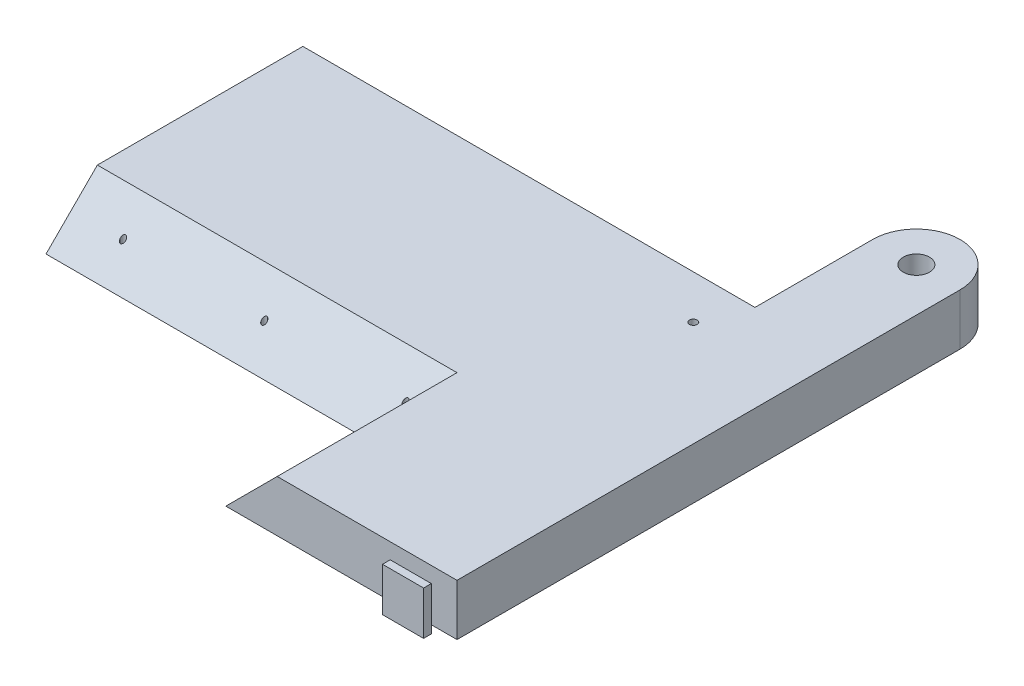
SolidWorks part; units mm, degrees
ref_plane "Front Plane" through (0, 0, 0) normal (0, 0, 1) x (1, 0, 0)
ref_plane "Top Plane" through (0, 0, 0) normal (0, 1, 0) x (1, 0, 0)
ref_plane "Right Plane" through (0, 0, 0) normal (1, 0, 0) x (0, 0, -1)
sketch "CornerSketch1" plane through (0, 0, 0) normal (0, 1, 0) x (1, 0, 0)
  line L0 (210, -50) -> (120, -50)
  line L2 (0, 100) -> (176, 100)
  line L5 (120, -50) -> (120, 0)
  line L6 (120, 0) -> (0, 0)
  line L7 (0, 100) -> (0, 0)
  line L8 (176, 145.825) -> (176, 100)
  line L10 (210, 145.825) -> (210, -50)
  arc A0 (210, 145.825) -> (176, 145.825) centre (193, 145.825) ccw
  dimension "D3" = 34
  dimension "D4" = 90
  dimension "D6" = 45.825
  dimension "D2" = 210
  dimension "D5" = 150
  dimension "D7" = 100
extrude "CornerBoss-Extrude1" add sketch "CornerSketch1" along normal blind 20
shell "Shell1" thickness 3 removed face at (126.5, 0, -51.0813)
sketch "PutBackPartOfShellSketch1" plane through (0, 17, 0) normal (0, -1, 0) x (1, 0, 0)
  line L0 (3, -3) -> (123, -3)
  line L1 (123, -3) -> (123, 47)
  line L2 (123, 47) -> (143, 47)
  line L3 (143, 47) -> (143, -23)
  line L4 (143, -23) -> (3, -23)
  line L5 (3, -3) -> (3, -23)
  line L6 (123, -3) -> (123, 47) construction
  line L9 (123, 47) -> (207, 47) construction
  line L10 (3, -97) -> (3, -3) construction
  line L11 (3, -97) -> (3, -3) construction
  line L12 (0, 0) -> (120, 0) construction
  dimension "D1" = 23
extrude "PutBackPartOfShellBoss-Extrude1" add sketch "PutBackPartOfShellSketch1" along normal blind 17
sketch "TabHoleCutsSketch1" plane through (0, 0, 0) normal (0, -1, 0) x (1, 0, 0)
  line L1 (120, 50) -> (210, 50) construction
  line L2 (0, -100) -> (0, 0) construction
  line L3 (120, 0) -> (120, 50) construction
  line L4 (0, 0) -> (120, 0) construction
  circle A0 centre (130, 30) radius 1
  circle A1 centre (130, -10) radius 1
  circle A2 centre (75, -10) radius 1
  circle A3 centre (20, -10) radius 1
  dimension "D4" = 2
  dimension "D2" = 55
  dimension "D3" = 20
  dimension "D5" = 20
  dimension "D6" = 10
  dimension "D1" = 10
extrude "TabHoleCuts-Extrude3" cut sketch "TabHoleCutsSketch1" against normal through all
sketch "PadSketch2" plane through (0, 17, 0) normal (0, -1, 0) x (1, 0, 0)
  line L0 (210, 50) -> (210, -145.825) construction
  line L1 (176, -100) -> (0, -100) construction
  circle A0 centre (193, -145.825) radius 12
  circle A1 centre (169, -83) radius 5
  dimension "D2" = 10
  dimension "D1" = 24
  dimension "D3" = 41
  dimension "D4" = 17
extrude "PadBoss-Extrude2" add sketch "PadSketch2" along normal blind 10
sketch "StepperRodHoleSketch3" plane through (0, 7, 0) normal (0, -1, 0) x (1, 0, 0)
  circle A0 centre (193, -145.825) radius 5.1
  circle A1 centre (169, -83) radius 1.5
  dimension "D2" = 3
  dimension "D1" = 10.2
extrude "StepperRodHoleCut-Extrude1" cut sketch "StepperRodHoleSketch3" against normal through all
sketch "ThreadedNutMountHolesSketch4" plane through (0, 7, 0) normal (0, -1, 0) x (-1, 0, 0)
  circle A8 centre (-193, 153.825) radius 1
  circle A9 centre (-185, 145.825) radius 1
  circle A10 centre (-201, 145.825) radius 1
  circle A11 centre (-193, 137.825) radius 1
  dimension "D1" = 2
  dimension "D3" = 16
  dimension "D4" = 8
  dimension "D5" = 16
extrude "ThreadedNutMountHolesCut-Extrude2" cut sketch "ThreadedNutMountHolesSketch4" against normal blind 10
sketch "TLPegHoleSketch1" plane through (0, 0, 0) normal (-1, 0, 0) x (0, 0, 1)
  line L1 (-90, 14) -> (-80, 14)
  line L2 (-90, 14) -> (-90, 0)
  line L3 (-90, 0) -> (-80, 0)
  line L4 (-80, 14) -> (-80, 0)
  line L7 (-100, 0) -> (0, 0) construction
  line L8 (-100, 20) -> (-100, 0) construction
  dimension "D1" = 10
  dimension "D2" = 10
  dimension "D3" = 14
extrude "TLPegHoleCut-Extrude1" cut sketch "TLPegHoleSketch1" against normal blind 3
sketch "BottomPegSketch2" plane through (0, 0, 50) normal (0, 0, 1) x (1, 0, 0)
  line L1 (190.1, 13.9) -> (199.9, 13.9)
  line L2 (190.1, 13.9) -> (190.1, 0)
  line L3 (190.1, 0) -> (199.9, 0)
  line L4 (199.9, 13.9) -> (199.9, 0)
  line L6 (210, 20) -> (210, 0) construction
  line L7 (120, 0) -> (210, 0) construction
  dimension "D2" = 13.9
  dimension "D3" = 9.8
  dimension "D1" = 10.1
extrude "BottomPegBoss-Extrude1" add sketch "BottomPegSketch2" along normal blind 3.1
sketch "BottomPegCapSketch3" plane through (0, 0, 53.1) normal (0, 0, 1) x (1, 0, 0)
  line L1 (187.1, 17) -> (203.1, 17)
  line L2 (187.1, 17) -> (187.1, 0)
  line L3 (187.1, 0) -> (203.1, 0)
  line L4 (203.1, 17) -> (203.1, 0)
  line L6 (120, 0) -> (190.1, 0) construction
  line L7 (190.1, 13.9) -> (190.1, 0) construction
  dimension "D1" = 16
  dimension "D3" = 17
  dimension "D2" = 3
extrude "BottomPegCapBoss-Extrude2" add sketch "BottomPegCapSketch3" along normal blind 3
chamfer "OverlapChamfer1" distance 20 distance2 20 2 edges at (120, 20, 25) (60, 20, 0)
equation "\"BedThickness\"= 20mm"
equation "\"BedToBuildPlateStandoffHolesDistanceFromLeftOrRight\"= \"BuildPlateStandoffHolesDistanceFromLeftOrRight\" + \"BedIncreasedByWidth\" / 2'Equals 17"
equation "\"BedToBuildPlateStandoffHolesDistanceFromBack\"= \"BuildPlateStandoffHolesDistanceFromBack\" + \"BedIncreasedByLength\" / 2'Equals 41"
equation "\"BedToBuildPlateStandoffHoleSize\"= 3mm"
equation "\"BedLLongSide\"= \"BedThirdSize\" * 3'Equals 210"
equation "\"BedLShortSide\"= \"BedThirdSize\" * 2'Equals 140"
equation "\"BedIncreasedByWidth\"= 20mm"
equation "\"BedIncreasedByLength\"= 0mm"
equation "\"BedThirdSize\"= 70mm"
equation "\"BedOverlap\"= 20mm"
equation "\"D2@TabHoleCutsSketch1\"= 55mm"
equation "\"D3@TabHoleCutsSketch1\" = \"BedOverlap\""
equation "\"D5@TabHoleCutsSketch1\" = \"BedOverlap\""
equation "\"D6@TabHoleCutsSketch1\" = \"BedOverlap\" / 2"
equation "\"D3@TLPegHoleSketch1\"=\"BedTopPegHoleHeight\""
equation "\"StandardWallThickness\"= 3mm"
equation "\"D1@CornerBoss-Extrude1\"=\"BedThickness\""
equation "\"D1@TLPegHoleCut-Extrude1\" = \"StandardWallThickness\""
equation "\"D1@BottomPegBoss-Extrude1\"=\"BedTopPegBoss\""
equation "\"D2@BottomPegCapSketch3\"=\"StandardWallThickness\""
equation "\"D1@BottomPegCapBoss-Extrude2\" = \"StandardWallThickness\""
equation "\"LeadScrewNutPadSize\"= \"LeadScrewNutMountingHoleFlangeDiameter\" + 2mm'Equals 24"
equation "\"BedToBuildPlateStandoffPadSize\"= 10mm"
equation "\"D1@PadSketch2\" = \"LeadScrewNutPadSize\""
equation "\"D2@PadSketch2\" = \"BedToBuildPlateStandoffPadSize\""
equation "\"D3@PadSketch2\"=\"BedToBuildPlateStandoffHolesDistanceFromBack\""
equation "\"D4@PadSketch2\"=\"BedToBuildPlateStandoffHolesDistanceFromLeftOrRight\""
equation "\"D2@StepperRodHoleSketch3\"=\"BedToBuildPlateStandoffHoleSize\""
equation "\"BuildPlateStandoffHolesDistanceFromLeftOrRight\"= 7mm"
equation "\"BuildPlateStandoffHolesDistanceFromBack\"= 41mm"
equation "\"D1@StepperRodHoleSketch3\"=\"LeadScrewNutInnerShaftFlangeDiameter\""
equation "\"BedLWidth\"= \"BedThirdSize\" + \"BedOverlap\"'Equals 90"
equation "\"D4@CornerSketch1\"=\"BedLWidth\" + \"BedIncreasedByLength\"/2"
equation "\"D2@CornerSketch1\"=\"BedLLongSide\""
equation "\"D7@CornerSketch1\"=\"BedLWidth\" +\"BedOverlap\"/2"
equation "\"DistanceFromBedSideToStepperHole\"= ( \"DistanceBetweenLeftToRightStepperHoles\" - \"BedWidth\" ) / 2'Equals 45.825"
equation "\"RailThickness\"= .125in'Spec"
equation "\"DistanceBetweenLeftToRightStepperHoles\"= \"FrontBackRailLength\" - \"StepperMountingHoleOffsetFromLeftOrRightSide\" * 2 - \"StepperMountingHoleDistance\"'Equals 461.65"
equation "\"BedInnerSquareWidth\"= \"BedThirdSize\" * 3'Equals 210"
equation "\"FrontBackRailLength\"= 510mm"
equation "\"StepperMountingHoleOffsetFromItsSide\"= 5.5mm'Spec"
equation "\"StepperMountingHoleOffsetFromLeftOrRightSide\"= \"StepperMountingHoleOffsetFromItsSide\" + \"RailThickness\""
equation "\"StepperMountingHoleDistance\"= 31mm'Spec"
equation "\"BedWidth\"= \"BedInnerSquareWidth\" + \"BedLWidth\" * 2 - \"BedOverlap\" * 2 + \"BedIncreasedByWidth\"'Equals 370"
equation "\"D6@CornerSketch1\"=\"DistanceFromBedSideToStepperHole\""
equation "\"DistanceFromBedFrontToStepperHole\"= \"LeadScrewNutPadSize\" + 10mm"
equation "\"D3@CornerSketch1\"=\"DistanceFromBedFrontToStepperHole\""
equation "\"D5@CornerSketch1\"=\"BedLShortSide\" +\"BedIncreasedByWidth\"/2"
equation "\"LeadScrewNutInnerShaftFlangeDiameter\"= 10.2mm'Spec"
equation "\"LeadScrewNutMountHoleDiameter\"= 2mm'Spec is 4.1 but smaller for tapping"
equation "\"LeadScrewNutMountingHoleFlangeDiameter\"= 22mm'Spec"
equation "\"LeadScrewNutMountingHoleDistance\"= 16mm'Spec"
equation "\"D3@ThreadedNutMountHolesSketch4\"=\"LeadScrewNutMountingHoleDistance\""
equation "\"D4@ThreadedNutMountHolesSketch4\"=\"LeadScrewNutMountingHoleDistance\"/2"
equation "\"D5@ThreadedNutMountHolesSketch4\"=\"LeadScrewNutMountingHoleDistance\""
equation "\"D2@ThreadedNutMountHolesSketch4\"=\"LeadScrewNutMountingHoleDistance\"/2"
equation "\"D1@ThreadedNutMountHolesSketch4\"=\"LeadScrewNutMountHoleDiameter\""
equation "\"LeadScrewNutPadDepth\"= \"BedThickness\" / 2'Equals 10"
equation "\"D1@ThreadedNutMountHolesCut-Extrude2\"=\"LeadScrewNutPadDepth\""
equation "\"D1@PadBoss-Extrude2\"= \"LeadScrewNutPadDepth\""
equation "\"BedTopPegHoleWidth\"= 10mm"
equation "\"BedTopPegHoleHeight\"= \"BedThickness\"- \"StandardWallThickness\"* 2' Equals 14"
equation "\"BedTopPegWidth\"= \"BedTopPegHoleWidth\"- .1mm* 2'For easier assembly"
equation "\"BedTopPegHeight\"= \"BedTopPegHoleHeight\"- .1mm'For easier assembly"
equation "\"BedTopPegOffsetFromSide\"= 10mm"
equation "\"BedTopPegBoss\"= \"StandardWallThickness\"+ .1mm'For easier assembly"
equation "\"BedTopPegCapHeight\"= \"BedThickness\"- \"StandardWallThickness\"'Equals 17"
equation "\"BedTopPegCapWidth\"= \"BedThickness\"/2 + \"StandardWallThickness\"*2'Equals 16"
equation "\"D1@TLPegHoleSketch1\"=\"BedTopPegOffsetFromSide\""
equation "\"D2@TLPegHoleSketch1\"=\"BedTopPegHoleWidth\""
equation "\"D3@BottomPegSketch2\"=\"BedTopPegWidth\""
equation "\"D2@BottomPegSketch2\"=\"BedTopPegHeight\""
equation "\"D1@BottomPegCapSketch3\"=\"BedTopPegCapWidth\""
equation "\"D3@BottomPegCapSketch3\"=\"BedTopPegCapHeight\""
equation "\"D1@PutBackPartOfShellSketch1\"=\"BedOverlap\" + \"StandardWallThickness\""
equation "\"D1@PutBackPartOfShellBoss-Extrude1\"=\"BedThickness\"- \"StandardWallThickness\""
equation "\"D1@OverlapChamfer1\"=\"BedThickness\""
equation "\"D3@OverlapChamfer1\" = \"BedOverlap\""
